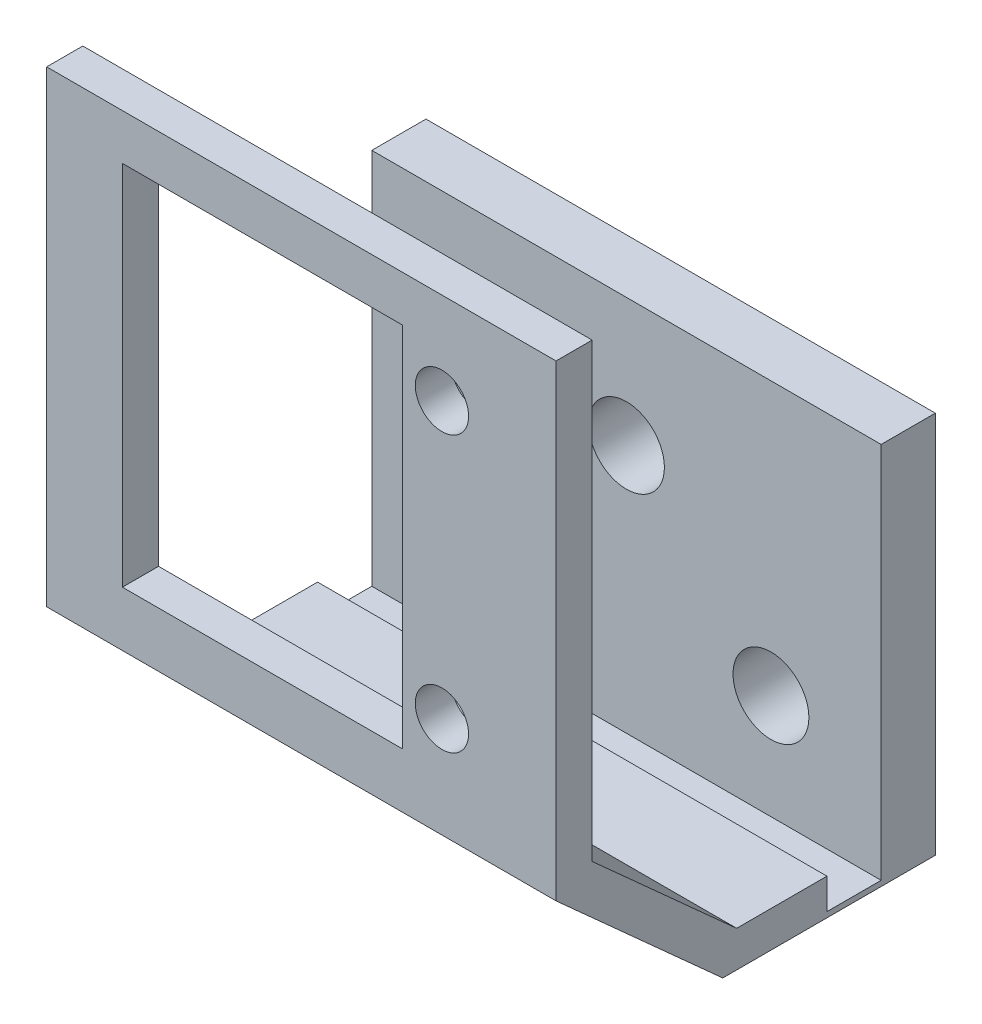
SolidWorks part; units mm, degrees
ref_plane "Front Plane" through (0, 0, 0) normal (0, 0, 1) x (1, 0, 0)
ref_plane "Top Plane" through (0, 0, 0) normal (0, 1, 0) x (1, 0, 0)
ref_plane "Right Plane" through (0, 0, 0) normal (1, 0, 0) x (0, 0, -1)
sketch "Sketch2" plane through (0, 0, 0) normal (0, 0, 1) x (1, 0, 0)
  line L1 (-76.6, -15) -> (-48.4, -15)
  line L2 (-76.6, -15) -> (-76.6, 6.2)
  line L3 (-76.6, 6.2) -> (-48.4, 6.2)
  line L4 (-48.4, -15) -> (-48.4, 6.2)
  line L5 (-50.4, -15) -> (-74.6, -15) construction
  line L6 (-48.4, -2) -> (-48.4, -13) construction
  line L7 (-74.6, 6.2) -> (-50.4, 6.2) construction
  circle A0 centre (-54.5, -8.9) radius 2.1
  circle A1 centre (-70.5, -8.9) radius 2.1
  circle A2 centre (-62.5, -0.9) radius 2.1
  circle A3 centre (-54.5, -8.9) radius 2.1 construction
  circle A4 centre (-70.5, -8.9) radius 2.1 construction
  circle A5 centre (-62.5, -0.9) radius 2.1 construction
  point P7 (-62.5, -15)
  point P8 (-62.5, -15)
extrude "Boss-Extrude1" add sketch "Sketch2" along normal blind 3
sketch "Sketch3" plane through (0, 0, 3) normal (0, 0, 1) x (1, 0, 0)
  line L0 (-76.6, 6.2) -> (-76.6, -15) construction
  line L1 (-48.4, -15) -> (-76.6, -15)
  line L2 (-48.4, -15) -> (-48.4, -14.7)
  line L3 (-48.4, -14.7) -> (-76.6, -14.7)
  line L4 (-76.6, -15) -> (-76.6, -14.7)
  dimension "D1" = 0.3
extrude "Boss-Extrude2" add sketch "Sketch3" along normal blind 3
sketch "Sketch6" plane through (-76.6, 0, 0) normal (-1, 0, 0) x (0, 0, 1)
  line L0 (6, -15) -> (11.7677, -15)
  line L1 (11.7677, -15) -> (21, -6.6872)
  line L2 (21, -6.6872) -> (21, 19.2032)
  line L3 (21, 19.2032) -> (19, 19.2032)
  line L4 (19, 19.2032) -> (19, -5.7968)
  line L5 (19, -5.7968) -> (11, -13)
  line L6 (11, -13) -> (6, -13)
  line L7 (6, -13) -> (6, -15)
  line L8 (3, 6.2) -> (3, -14.7) construction
  dimension "D1" = 2
  dimension "D2" = 2
  dimension "D3" = 2
  dimension "D4" = 42
  dimension "D5" = 25
  dimension "D6" = 5
  dimension "D7" = 16
extrude "Boss-Extrude5" add sketch "Sketch6" against normal up to surface (28.2 mm away) up to face at (-48.4, -7.8333, 3)
sketch "Sketch7" plane through (0, 0, 21) normal (0, 0, 1) x (1, 0, 0)
  line L1 (-72.406, 16.672) -> (-56.886, 16.672)
  line L2 (-72.406, 16.672) -> (-72.406, -3.648)
  line L3 (-72.406, -3.648) -> (-56.886, -3.648)
  line L4 (-52.086, 16.672) -> (-52.086, -3.648) construction
  line L5 (-48.4, 19.2032) -> (-76.6, 19.2032) construction
  line L6 (-56.886, -3.648) -> (-56.886, 16.672)
  line L7 (-56.886, 16.672) -> (-52.086, 16.672) construction
  line L8 (-56.886, -3.648) -> (-52.086, -3.648) construction
  line L9 (-48.4, 19.2032) -> (-48.4, -6.6872) construction
  line L10 (-54.716, 14.132) -> (-54.716, -1.108) construction
  circle A0 centre (-54.716, -1.108) radius 1.475
  circle A1 centre (-54.716, 14.132) radius 1.475
  point P0 (-62.5, 6.258)
  point P8 (-62.5, 19.2032)
  point P12 (-54.716, 6.512)
  point P13 (-52.086, 6.512)
  point P18 (-48.4, 6.258)
  dimension "D7" = 2.95
  dimension "D1" = 10.414
  dimension "D2" = 9.906
  dimension "D3" = 20.32
  dimension "D4" = 20.32
  dimension "D5" = 4.8
  dimension "D6" = 15.24
  dimension "D8" = 2.63
extrude "Cut-Extrude1" cut sketch "Sketch7" against normal up to next
equation "\"D2@Sketch6\"=\"D1@Sketch6\""
equation "\"D3@Sketch6\"=\"D2@Sketch6\""
equation "\"width\"= 24"
equation "\"thk\"= 3"
equation "\"holesize\"= 4.2"
equation "\"holedistance\"= ( 20 + 12 ) / 2"
equation "\"threaded_hole\"= 3.9"
equation "\"fillet_radius\"= 2"
equation "\"ground_clearance\"= 25"
equation "\"tire_thk\"= 3"
equation "\"innerwheel_diam\" = \"wheel_diam\"-2*\"tire_thk\""
equation "\"innerwheel_thk\"= 8"
equation "\"wheel_diam\"= 2*(\"width\"/2+\"ground_clearance\")"
equation "\"coloursensor_holesize\"= 2.65"
equation "\"hole_to_edge\" = 4"
equation "\"D7@Sketch7\"=\"coloursensor_holesize\"+0.3"
